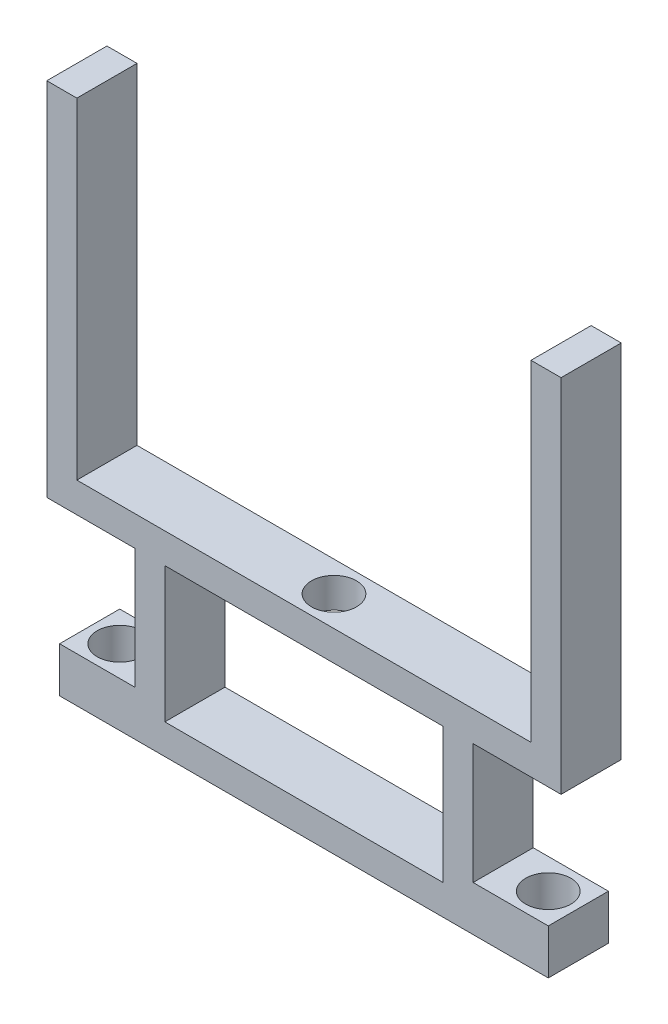
SolidWorks part; units mm, degrees
ref_plane "Front Plane" through (0, 0, 0) normal (0, 0, 1) x (1, 0, 0)
ref_plane "Top Plane" through (0, 0, 0) normal (0, 1, 0) x (1, 0, 0)
ref_plane "Right Plane" through (0, 0, 0) normal (1, 0, 0) x (0, 0, -1)
sketch "Sketch1" plane through (0, 0, 0) normal (0, 1, 0) x (1, 0, 0)
  line L0 (0, 0) -> (28.5, 0)
  line L1 (-55, 0) -> (55, 0) construction
  line L3 (0, 2) -> (30.5, 2)
  line L4 (0, -55) -> (0, 55) construction
  line L5 (30.5, 2) -> (30.5, -2)
  line L6 (30.5, -2) -> (-2, -2)
  line L7 (-2, -2) -> (-2, 2)
  line L8 (-2, 2) -> (0, 2)
  circle A0 centre (0, 0) radius 1.5
  circle A1 centre (28.5, 0) radius 1.5
  dimension "D2" = 3
  dimension "D3" = 3
  dimension "D1" = 28.5
  dimension "D4" = 4
  dimension "D5" = 2
  dimension "D6" = 2
  dimension "D7" = 2
extrude "Boss-Extrude1" add sketch "Sketch1" along normal blind 3 contours L8 L7 L6 L5 L3 A1 A0 region at (15.25, 0, -1.6725)
sketch "Sketch2" plane through (0, 3, 0) normal (0, 1, 0) x (1, 0, 0)
  line L0 (-2, 2) -> (30.5, 2) construction
  line L1 (3, 2) -> (25.5, 2)
  line L2 (3, 2) -> (3, -2)
  line L3 (3, -2) -> (25.5, -2)
  line L4 (25.5, 2) -> (25.5, -2)
  line L5 (30.5, -2) -> (-2, -2) construction
  circle A0 centre (28.5, 0) radius 1.5 construction
  dimension "D1" = 3
  dimension "D2" = 3
extrude "Boss-Extrude2" add sketch "Sketch2" along normal blind 10
sketch "Sketch3" plane through (0, 0, 2) normal (0, 0, 1) x (1, 0, 0)
  line L0 (3, 13) -> (25.5, 13) construction
  line L1 (5, 2) -> (23.5, 2)
  line L2 (5, 2) -> (5, 11)
  line L3 (5, 11) -> (23.5, 11)
  line L4 (23.5, 2) -> (23.5, 11)
  line L5 (3, 13) -> (3, 3) construction
  line L6 (25.5, 13) -> (25.5, 3) construction
  line L7 (30.5, 3) -> (25.5, 3) construction
  dimension "D1" = 2
  dimension "D2" = 2
  dimension "D3" = 2
  dimension "D4" = 1
extrude "Cut-Extrude1" cut sketch "Sketch3" against normal blind 10
sketch "Sketch4" plane through (0, 13, 0) normal (0, 1, 0) x (1, 0, 0)
  line L1 (-55, 0) -> (55, 0) construction
  line L3 (-0.85, 0) -> (-0.85, 2)
  line L4 (25.5, 2) -> (3, 2) construction
  line L5 (-0.85, 2) -> (-0.85, -2)
  line L6 (3, -2) -> (25.5, -2) construction
  line L7 (-0.85, -2) -> (29.35, -2)
  line L8 (29.35, -2) -> (29.35, 0)
  line L9 (-0.85, 2) -> (29.35, 2)
  line L10 (29.35, 2) -> (29.35, 0)
  line L11 (3, 2) -> (3, -2) construction
  line M1 (3, 2) -> (3, -2)
  line M2 (3, -2) -> (25.5, -2)
  line M3 (25.5, -2) -> (25.5, 2)
  line M4 (25.5, 2) -> (3, 2)
  dimension "D1" = 30.2
  dimension "D2" = 3.85
extrude "Boss-Extrude3" add sketch "Sketch4" against normal blind 2 contours L9 L3 L5 L7 M1 | M4 M1 M2 M3 | L10 L9 L7 L8 M3 region at (1.075, 13, 0) region at (14.25, 13, 0) region at (27.425, 13, 0)
sketch "Sketch5" plane through (0, 13, 0) normal (0, 1, 0) x (1, 0, 0)
  line L0 (-7.15, 0) -> (7.15, 0) construction
  line L1 (29.35, 2) -> (29.35, -2) construction
  circle A0 centre (14.25, 0) radius 1.5
  dimension "D1" = 3
  dimension "D2" = 15.1
extrude "Cut-Extrude2" cut sketch "Sketch5" against normal blind 2
sketch "Sketch6" plane through (-0.85, 0, 0) normal (-1, 0, 0) x (0, 0, 1)
  line L1 (-2, 13) -> (2, 13)
  line L2 (-2, 13) -> (-2, 11)
  line L3 (-2, 11) -> (2, 11)
  line L4 (2, 13) -> (2, 11)
extrude "Boss-Extrude4" add sketch "Sketch6" along normal blind 2
sketch "Sketch7" plane through (0, 13, 0) normal (0, 1, 0) x (1, 0, 0)
  line L0 (29.35, 2) -> (-2.85, 2) construction
  line L1 (-2.85, -2) -> (-0.85, -2)
  line L2 (-2.85, -2) -> (-2.85, 2)
  line L3 (-2.85, 2) -> (-0.85, 2)
  line L4 (-0.85, -2) -> (-0.85, 2)
  dimension "D1" = 2
extrude "Boss-Extrude5" add sketch "Sketch7" along normal blind 22
sketch "Sketch8" plane through (29.35, 0, 0) normal (1, 0, 0) x (0, 0, -1)
  line L1 (-2, 11) -> (2, 11)
  line L2 (-2, 11) -> (-2, 13)
  line L3 (-2, 13) -> (2, 13)
  line L4 (2, 11) -> (2, 13)
extrude "Boss-Extrude6" add sketch "Sketch8" along normal blind 2
sketch "Sketch9" plane through (0, 13, 0) normal (0, 1, 0) x (1, 0, 0)
  line L0 (-0.85, -2) -> (31.35, -2) construction
  line L1 (31.35, 2) -> (29.35, 2)
  line L2 (31.35, 2) -> (31.35, -2)
  line L3 (31.35, -2) -> (29.35, -2)
  line L4 (29.35, 2) -> (29.35, -2)
  dimension "D1" = 2
extrude "Boss-Extrude7" add sketch "Sketch9" along normal blind 22
